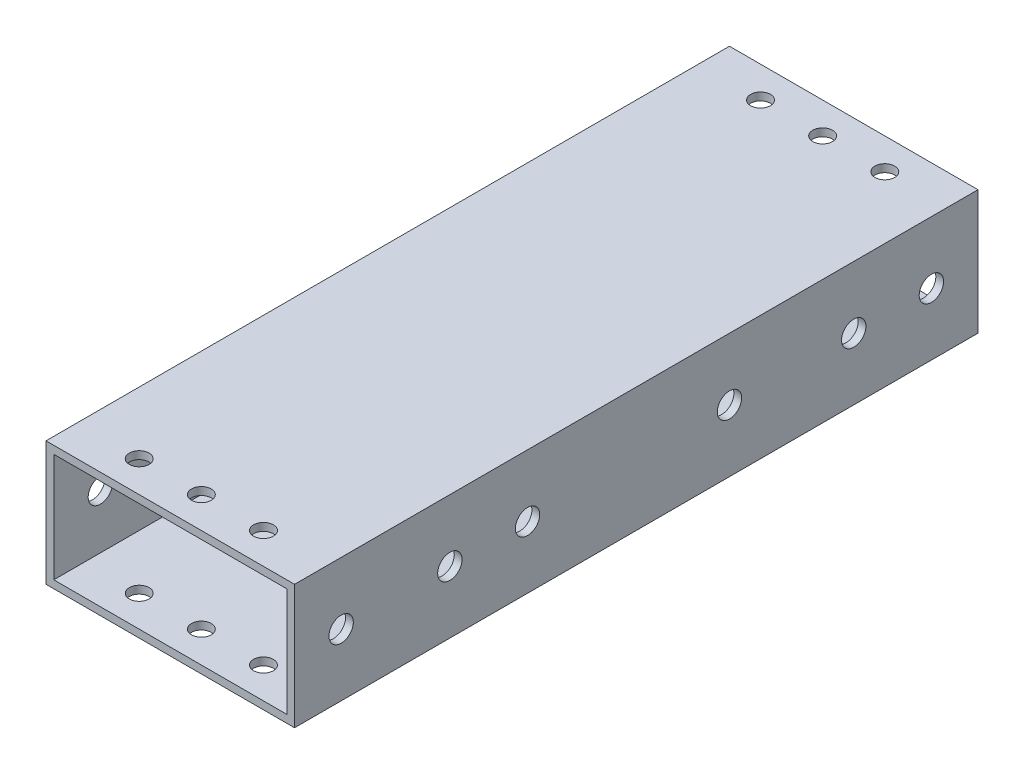
SolidWorks part; units mm, degrees
material "6061-T6 (SS)"
ref_plane "Front Plane" through (0, 0, 0) normal (0, 0, 1) x (1, 0, 0)
ref_plane "Top Plane" through (0, 0, 0) normal (0, 1, 0) x (1, 0, 0)
ref_plane "Right Plane" through (0, 0, 0) normal (1, 0, 0) x (0, 0, -1)
sketch "Sketch1" plane through (0, 0, 0) normal (0, 0, 1) x (1, 0, 0)
  line L0 (-23.8125, 11.1125) -> (23.8125, 11.1125)
  line L1 (-25.4, -12.7) -> (25.4, -12.7)
  line L2 (-25.4, -12.7) -> (-25.4, 12.7)
  line L3 (-25.4, 12.7) -> (25.4, 12.7)
  line L4 (25.4, -12.7) -> (25.4, 12.7)
  line L5 (-25.4, -12.7) -> (25.4, 12.7) construction
  line L6 (-25.4, 12.7) -> (25.4, -12.7) construction
  line L7 (23.8125, -11.1125) -> (23.8125, 11.1125)
  line L8 (-23.8125, -11.1125) -> (23.8125, -11.1125)
  line L9 (-23.8125, -11.1125) -> (-23.8125, 11.1125)
  point P0 (0, 0)
  dimension "D1" = 50.8
  dimension "D2" = 25.4
  dimension "D3" = 1.5875
extrude "Boss-Extrude1" add sketch "Sketch1" along normal mid plane 139.7
sketch "Sketch2" plane through (0, 12.7, 0) normal (0, 1, 0) x (1, 0, 0)
  line L0 (25.4, 69.85) -> (-25.4, 69.85) construction
  line L1 (25.4, 0) -> (-25.4, 0) construction
  line L2 (25.4, -69.85) -> (25.4, 69.85) construction
  line L3 (-25.4, -69.85) -> (-25.4, 69.85) construction
  circle A0 centre (-12.7, 63.5) radius 2.0193
  circle A1 centre (0, 63.5) radius 2.0193
  circle A2 centre (12.7, 63.5) radius 2.0193
  circle A3 centre (12.7, -63.5) radius 2.0193
  circle A4 centre (0, -63.5) radius 2.0193
  circle A5 centre (-12.7, -63.5) radius 2.0193
  dimension "D1" = 4.0386
  dimension "D2" = 12.7
  dimension "D3" = 12.7
  dimension "D4" = 6.35
extrude "Cut-Extrude1" cut sketch "Sketch2" against normal through all
sketch "Sketch3" plane through (25.4, 0, 0) normal (1, 0, 0) x (0, 0, -1)
  line L0 (0, 12.7) -> (0, -12.7) construction
  line L1 (-69.85, 12.7) -> (69.85, 12.7) construction
  line L2 (-69.85, -12.7) -> (69.85, -12.7) construction
  line L3 (-69.85, -12.7) -> (-69.85, 12.7) construction
  line L5 (69.85, -12.7) -> (69.85, 12.7) construction
  circle A8 centre (60.325, 0) radius 2.4892
  circle A9 centre (44.45, 0) radius 2.4892
  circle A10 centre (19.05, 0) radius 2.4892
  circle A11 centre (-60.325, 0) radius 2.4892
  circle A14 centre (-38.1, 0) radius 2.4892
  circle A15 centre (-22.225, 0) radius 2.4892
  dimension "D1" = 9.525
  dimension "D3" = 47.625
  dimension "D8" = 4.9784
  dimension "D2" = 22.225
  dimension "D6" = 15.875
  dimension "D7" = 25.4
extrude "Cut-Extrude2" cut sketch "Sketch3" against normal through all
